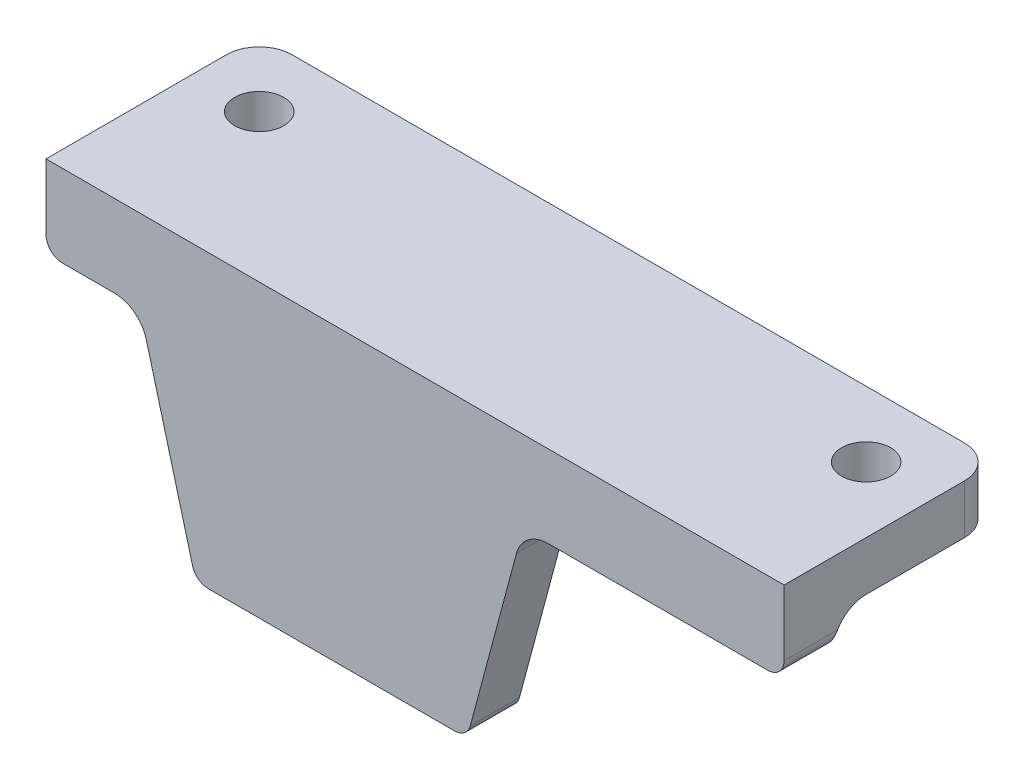
SolidWorks part; units mm, degrees
ref_plane "Front Plane" through (0, 0, 0) normal (0, 0, 1) x (1, 0, 0)
ref_plane "Top Plane" through (0, 0, 0) normal (0, 1, 0) x (1, 0, 0)
ref_plane "Right Plane" through (0, 0, 0) normal (1, 0, 0) x (0, 0, -1)
sketch "Sketch1" plane through (0, 0, 0) normal (0, 0, 1) x (1, 0, 0)
  line L1 (-15.9, -6.25) -> (15.9, -6.25)
  line L2 (-15.9, -6.25) -> (-15.9, 6.25)
  line L3 (-15.9, 6.25) -> (15.9, 6.25)
  line L4 (15.9, -6.25) -> (15.9, 6.25)
  line L5 (-15.9, -6.25) -> (15.9, 6.25) construction
  line L6 (-15.9, 6.25) -> (15.9, -6.25) construction
  line L7 (11.7, -6.25) -> (-11.7, -6.25)
  line L8 (11.7, -6.25) -> (11.7, 6.25)
  line L9 (11.7, 6.25) -> (-11.7, 6.25)
  line L10 (-11.7, -6.25) -> (-11.7, 6.25)
  line L11 (11.7, -6.25) -> (-11.7, 6.25) construction
  line L12 (11.7, 6.25) -> (-11.7, -6.25) construction
  circle A0 centre (-14.4, 0) radius 1
  circle A1 centre (-14.4, 3.5) radius 1
  circle A2 centre (-14.4, -3.5) radius 1
  circle A3 centre (14.4, 0) radius 1
  circle A4 centre (14.4, 3.5) radius 1
  circle A5 centre (14.4, -3.5) radius 1
  point P0 (0, 0)
  point P20 (0, 0)
  dimension "D3" = 2
  dimension "D1" = 31.8
  dimension "D2" = 12.5
  dimension "D4" = 1.5
  dimension "D5" = 3.5
  dimension "D6" = 3.5
  dimension "D7" = 1.5
  dimension "D8" = 23.4
sketch "Sketch3" plane through (0, 0, 0) normal (0, 0, 1) x (1, 0, 0)
  line L2 (2.4, -6) -> (-12.6, -6)
  line L3 (-13.5659, -5.2588) -> (-16.3865, 5.2676)
  line L7 (3.3659, -5.2588) -> (6.1865, 5.2676)
  line L12 (-22.5, 11.75) -> (22.5, 11.75)
  line L14 (-18.3183, 6.75) -> (-21.5, 6.75)
  line L15 (-22.5, 7.75) -> (-22.5, 11.75)
  line L16 (8.1183, 6.75) -> (21.5, 6.75)
  line L17 (22.5, 7.75) -> (22.5, 11.75)
  arc A3 (-12.6, -6) -> (-13.5659, -5.2588) centre (-12.6, -5) cw
  arc A5 (3.3659, -5.2588) -> (2.4, -6) centre (2.4, -5) cw
  arc A8 (-16.3865, 5.2676) -> (-18.3183, 6.75) centre (-18.3183, 4.75) ccw
  arc A9 (8.1183, 6.75) -> (6.1865, 5.2676) centre (8.1183, 4.75) ccw
  arc A10 (-21.5, 6.75) -> (-22.5, 7.75) centre (-21.5, 7.75) cw
  arc A11 (22.5, 7.75) -> (21.5, 6.75) centre (21.5, 7.75) cw
  circle A12 centre (0, 0) radius 3.5 construction
  point P0 (15.5155, 6.75)
  point P1 (0, 11.75)
  point P2 (-5.1, -6)
  point P25 (-13.8476, -6)
  point P46 (-16.7837, 6.75)
  point P49 (6.5837, 6.75)
  dimension "D9" = 17.4
  dimension "D10" = 1
  dimension "D6" = 1
  dimension "D14" = 2
  dimension "D15" = 2
  dimension "D16" = 1
  dimension "D17" = 1
  dimension "D20" = 7
  dimension "D3" = 75
  dimension "D4" = 6
  dimension "D5" = 11.75
  dimension "D7" = 75
  dimension "D8" = 15
  dimension "D18" = 45
  dimension "D19" = 5
extrude "Boss-Extrude1" add sketch "Sketch3" along normal blind 3
sketch "Sketch4" plane through (0, 0, 0) normal (0, 0, -1) x (-1, 0, 0)
  line L2 (22.5, 11.75) -> (22.5, 7.75) construction
  line L3 (-22.5, 11.75) -> (22.5, 11.75)
  line L4 (-22.5, 11.75) -> (-22.5, 8.75)
  line L5 (-22.5, 8.75) -> (22.5, 8.75)
  line L6 (22.5, 11.75) -> (22.5, 8.75)
  point P9 (-22.5, 8.75)
  point P12 (22.5, 8.75)
  dimension "D1" = 3
extrude "Boss-Extrude2" add sketch "Sketch4" along normal blind 10
fillet "Fillet1" radius 2 1 edges at (0, 8.75, 0)
fillet "Fillet2" radius 2 2 edges at (-22.5, 10.25, -10) (22.5, 10.25, -10)
sketch "Sketch5" plane through (0, 8.75, 0) normal (0, -1, 0) x (1, 0, 0)
  line L0 (-22.5, -8) -> (-22.5, -2) construction
  line L2 (20.5, -10) -> (-20.5, -10) construction
  circle A0 centre (-18.5, -6) radius 1.5
  dimension "D1" = 3
  dimension "D2" = 4
  dimension "D3" = 4
extrude "Cut-Extrude1" cut sketch "Sketch5" against normal through all
mirror "Mirror1" about plane through (0, 0, 0) normal (1, 0, 0) of "Cut-Extrude1"
sketch "Sketch6" plane through (0, 0, 0) normal (0, 0, -1) x (-1, 0, 0)
  line L0 (22.5, 11.75) -> (22.5, 8.75) construction
  circle A0 centre (5.1, 0) radius 3.5
  point P3 (5.4699, -1.4919)
  dimension "D1" = 7
  dimension "D2" = 17.4
extrude "Boss-Extrude3" add sketch "Sketch6" along normal blind 16
ref_plane "Plane3" through (-8.6, 0, 0) normal (-1, 0, 0) x (0, 0, 1)
ref_plane "Plane4" through (-1.6, 0, 0) normal (1, 0, 0) x (0, 0, -1)
ref_plane "Plane5" through (-5.1, 0, 0) normal (1, 0, 0) x (0, 0, -1)
fillet "Fillet3" radius 0.5 1 edges at (-8.6, 0, -16)
sketch "Sketch7" plane through (-5.1, 0, 0) normal (1, 0, 0) x (0, 0, -1)
  line L0 (8, 8.75) -> (2, 8.75) construction
  line L1 (0, 0) -> (10, 0)
  line L2 (0, 0) -> (0, 8.75)
  line L3 (0, 8.75) -> (10, 8.75)
  line L4 (10, 0) -> (10, 8.75)
  line L5 (10, 11.75) -> (10, 8.75) construction
  point P8 (1.4355, 0.1892)
extrude "Boss-Extrude4" add sketch "Sketch7" along normal mid plane 3 contours L4 L3 L2 L1
fillet "Fillet4" radius 1 9 edges at (-5.1, 3.5, -10) (-6.6, 8.75, -6) (-6.6, 8.1642, -0.5858) (-3.6, 8.75, -6) (-3.6, 8.1642, -0.5858) (-6.6, 3.1623, -5) (-3.6, 3.1623, -5) (-6.6, 4.9561, 0) (-3.6, 4.9561, 0)
equation "\"D6@Sketch1\"=\"D5@Sketch1\""
equation "\"D7@Sketch1\"=\"D4@Sketch1\""
